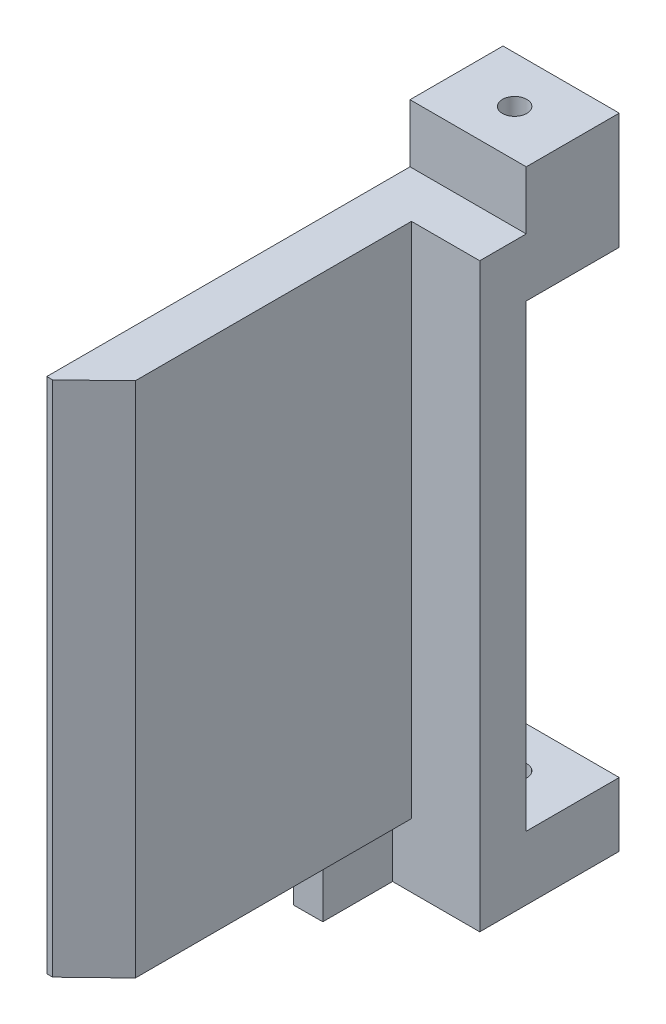
SolidWorks part; units mm, degrees
ref_plane "Спереди" through (0, 0, 0) normal (0, 0, 1) x (1, 0, 0)
ref_plane "Сверху" through (0, 0, 0) normal (0, 1, 0) x (1, 0, 0)
ref_plane "Справа" through (0, 0, 0) normal (1, 0, 0) x (0, 0, -1)
sketch "Эскиз1" plane through (0, 139.196, 0) normal (0, 1, 0) x (1, 0, 0)
  line L0 (21.559, -32.2731) -> (1.559, -32.2731)
  line L1 (1.559, 34.1) -> (1.559, -34.1) construction
  line L2 (21.559, -32.2731) -> (1.559, -32.2731) construction
  line L3 (1.559, -32.2731) -> (1.559, -68.3041)
  line L4 (1.559, -68.3041) -> (6.559, -68.2731)
  line L5 (6.559, -68.2731) -> (6.559, -56.2731)
  line L6 (6.559, -56.2731) -> (21.559, -56.2731)
  line L7 (21.559, -56.2731) -> (21.559, -32.2731)
  circle A0 centre (11.559, -40.2731) radius 2.1
extrude "Бобышка-Вытянуть1" add sketch "Эскиз1" along normal blind 11
ref_plane "Плоскость4" through (0, 150.196, 0) normal (0, 1, 0) x (1, 0, 0)
sketch "Эскиз2" plane through (0, 150.196, 0) normal (0, 1, 0) x (1, 0, 0)
  line L0 (1.559, -32.2731) -> (4.559, -32.2731)
  line L1 (21.559, -32.2731) -> (1.559, -32.2731) construction
  line L2 (4.559, -32.2731) -> (4.559, -48.2731)
  line L3 (4.559, -48.2731) -> (21.559, -48.2731)
  line L4 (21.559, -56.2731) -> (21.559, -32.2731) construction
  line L5 (108.059, -48.2731) -> (21.559, -48.2731) construction
  line L6 (21.559, -48.2731) -> (21.559, -56.2731)
  line L7 (21.559, -56.2731) -> (9.809, -56.2731)
  line L8 (6.559, -56.2731) -> (21.559, -56.2731) construction
  line L9 (9.809, -56.2731) -> (9.809, -103.7731)
  line L10 (9.809, -103.7731) -> (2.559, -110.7731)
  line L11 (2.559, -110.7731) -> (1.559, -110.7731)
  line L12 (1.559, 34.1) -> (1.559, -34.1) construction
  line L13 (1.559, -110.7731) -> (1.559, -32.2731)
extrude "Бобышка-Вытянуть2" add sketch "Эскиз2" along normal blind 79
sketch "Эскиз3" plane through (0, 239.196, 0) normal (0, 1, 0) x (1, 0, 0)
  line L0 (1.559, -32.2731) -> (1.559, -110.7731)
  line L1 (1.559, -110.7731) -> (2.559, -110.7731)
  line L2 (2.559, -110.7731) -> (9.809, -103.7731)
  line L3 (9.809, -103.7731) -> (9.809, -56.2731)
  line L4 (9.809, -56.2731) -> (21.559, -56.2731)
  line L5 (21.559, -56.2731) -> (21.559, -32.2731)
  line L6 (21.559, -32.2731) -> (1.559, -32.2731)
  circle A0 centre (11.559, -40.2731) radius 2.1
extrude "Бобышка-Вытянуть3" add sketch "Эскиз3" along normal blind 10
ref_plane "Плоскость5" through (0, 249.196, 0) normal (0, 1, 0) x (1, 0, 0)
sketch "Эскиз5" plane through (0, 249.196, 0) normal (0, 1, 0) x (1, 0, 0)
  line L0 (1.559, -110.7731) -> (1.559, -48.2731)
  line L1 (1.559, -32.2731) -> (1.559, -110.7731) construction
  line L2 (1.559, -48.2731) -> (21.559, -48.2731)
  line L3 (21.559, -48.2731) -> (21.559, -56.2731)
  line L4 (21.559, -56.2731) -> (9.809, -56.2731)
  line L5 (9.809, -56.2731) -> (9.809, -103.7731)
  line L6 (9.809, -103.7731) -> (2.559, -110.7731)
  line L7 (2.559, -110.7731) -> (1.559, -110.7731)
extrude "Бобышка-Вытянуть4" add sketch "Эскиз3<2>" against normal blind 10
sketch "Эскиз3<2>" plane through (0, 239.196, 0) normal (0, 1, 0) x (1, 0, 0) same geometry as "Эскиз3"
extrude "Вырез-Вытянуть6" cut sketch "Эскиз5" against normal blind 10
